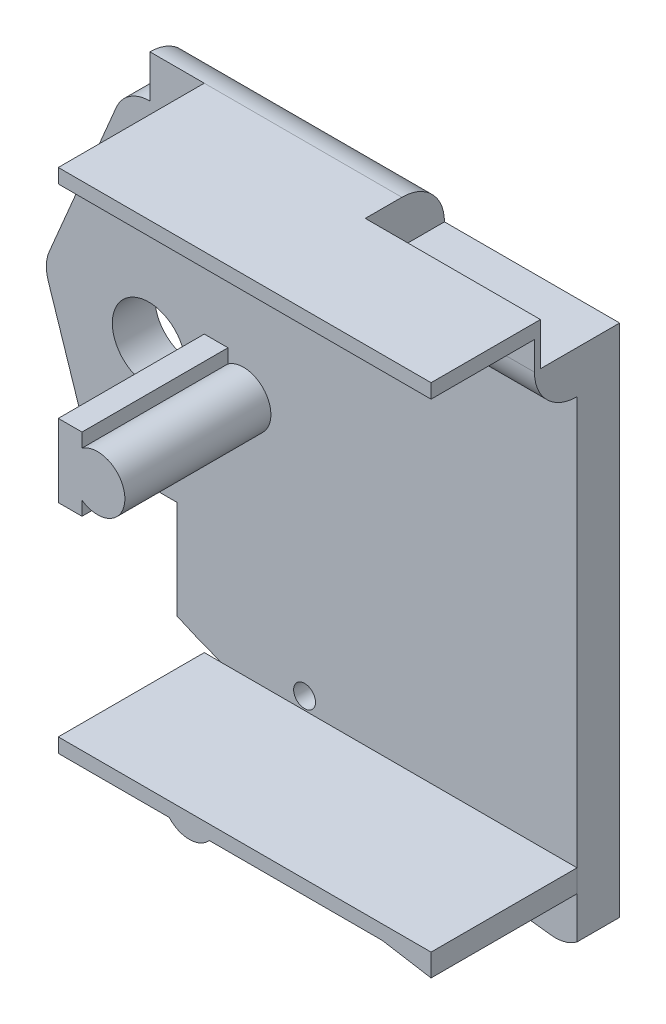
SolidWorks part; units mm, degrees
ref_plane "Спереди" through (0, 0, 0) normal (0, 0, 1) x (1, 0, 0)
ref_plane "Сверху" through (0, 0, 0) normal (0, 1, 0) x (1, 0, 0)
ref_plane "Справа" through (0, 0, 0) normal (1, 0, 0) x (0, 0, -1)
sketch "Эскиз2" plane through (0, 0, 0) normal (0, 0, 1) x (1, 0, 0)
  line L0 (-56.0468, 57.8448) -> (-56.0468, -75.1952)
  line L1 (-186.2888, 51.7421) -> (-204.676, 8.2939)
  line L4 (-193.5028, -33.6946) -> (-169.7062, -33.6946)
  line L5 (-169.7062, -33.6946) -> (-169.7062, -60.6352)
  line L24 (-193.5028, -33.6946) -> (-204.9691, 1.2814)
  line L27 (-177.0796, 57.8448) -> (-56.0468, 57.8448)
  arc A1 (-204.676, 8.2939) -> (-204.9691, 1.2814) centre (-195.4667, 4.3966) ccw
  arc A2 (-186.2888, 51.7421) -> (-177.0796, 57.8448) centre (-177.0796, 47.8448) cw
  arc A3 (-67.1233, -85.137) -> (-56.0468, -75.1952) centre (-66.0468, -75.1952) ccw
  circle A15 centre (-134.7062, -62.1552) radius 3
  spline S1 degree 3 poles (-169.7062, -60.6352) (-159.6635, -65.3294) (-148.3339, -68.8072) (-114.3227, -77.8089) (-90.3681, -82.6201) (-67.1233, -85.137) knots 0.055135 0.055135 0.055135 0.055135 0.172676 0.181905 0.429838 0.429838 0.429838 0.429838
  dimension "D1" = 10
  dimension "D2" = 10
ref_plane "?????25" through (0, 0, 53) normal (0, 0, 1) x (1, 0, 0)
sketch "Эскиз3" plane through (0, 0, 53) normal (0, 0, 1) x (-1, 0, 0)
  line L0 (54.8754, -65.5997) -> (54.8754, -69.5161)
  line L1 (54.8754, 72.6089) -> (54.8754, 65.5997)
  line L3 (155.6874, 10.0166) -> (162.1868, 10.0166)
  line L4 (155.6874, 10.0166) -> (155.6874, 6.196)
  line L6 (155.6874, -9.9834) -> (162.1868, -9.9834)
  line L8 (162.1868, 10.0166) -> (162.1868, -9.9834)
  line L10 (155.6874, -6.1628) -> (155.6874, -9.9834)
  line L15 (204.9076, -65.5997) -> (54.8754, -65.5997)
  line L16 (204.6318, -69.5161) -> (204.9076, -65.5997)
  line L17 (204.6318, -69.5161) -> (54.8754, -69.5161)
  line L19 (133.5844, 65.5997) -> (54.8754, 65.5997)
  line L20 (204.9076, 65.5997) -> (133.5844, 65.5997)
  line L21 (204.6318, 69.5161) -> (204.9076, 65.5997)
  line L22 (131.7963, 69.5161) -> (204.6318, 69.5161)
  line L23 (73.4325, 69.5161) -> (120.8114, 69.5161)
  line L25 (73.4325, 69.5161) -> (54.8754, 72.6089)
  arc A0 (155.6874, 6.196) -> (155.6874, -6.1628) centre (151.4371, 0.0166) ccw
  arc A7 (120.8114, 69.5161) -> (131.7963, 69.5161) centre (126.3039, 64.642) cw
  point P4 (158.9371, 0.0166)
  dimension "D1" = 15
  dimension "D2" = 20
extrude "Бобышка-Вытянуть1" add sketch "Эскиз3" against normal blind 40
extrude "Бобышка-Вытянуть2" add sketch "Эскиз2" along normal blind 13 separate body
sketch "Эскиз4" plane through (-56.0468, 0, 0) normal (1, 0, 0) x (0, 0, -1)
  line L0 (-21.7224, 65.5997) -> (-13, 65.5997)
  line L2 (-13, 65.5997) -> (-13, 57.8448)
  line L3 (-13, 57.8448) -> (-1.3287, 57.8448)
  arc A0 (-1.3287, 57.8448) -> (-21.7224, 65.5997) centre (-13, 57.8448) ccw
extrude "Бобышка-Вытянуть3" add sketch "Эскиз4" against normal up to vertex (148.8609 mm away) up to point (-204.9076, 65.5997, 53)
sketch "Эскиз5" plane through (-56.0468, 0, 0) normal (1, 0, 0) x (0, 0, -1)
  line L0 (-13, 69.5161) -> (-24.6713, 69.5161)
  line L1 (-13, 69.5161) -> (-53, 69.5161) construction
  line L2 (-24.6713, 69.5161) -> (-24.6713, 57.8448)
  arc A0 (-24.6713, 57.8448) -> (-13, 69.5161) centre (-13, 57.8448) ccw
extrude "Бобышка-Вытянуть4" add sketch "Эскиз5" against normal blind 55
sketch "Эскиз6" plane through (-56.0468, 0, 0) normal (1, 0, 0) x (0, 0, -1)
  line L0 (-23.0301, 57.8448) -> (-23.0301, 69.5161)
  line L1 (-13, 69.5161) -> (-53, 69.5161) construction
  line L2 (-23.0301, 69.5161) -> (0, 69.5161)
  line L3 (0, 69.5161) -> (0, 57.8448)
  line L4 (0, 57.8448) -> (-23.0301, 57.8448)
extrude "Вырез-Вытянуть1" cut sketch "Эскиз6" against normal blind 52
sketch "Эскиз7" plane through (0, 0, 13) normal (0, 0, -1) x (-1, 0, 0)
  line L1 (54.8754, 69.5161) -> (56.0468, 69.5161)
  line L2 (54.8754, 69.5161) -> (54.8754, 65.5997)
  line L3 (54.8754, 65.5997) -> (56.0468, 65.5997)
  line L4 (56.0468, 69.5161) -> (56.0468, 65.5997)
extrude "Вырез-Вытянуть2" cut sketch "Эскиз7" against normal blind 52
sketch "Эскиз8" plane through (0, 0, 13) normal (0, 0, -1) x (-1, 0, 0)
  line L0 (56.0468, -75.1952) -> (56.0468, 57.8448) construction
  line L1 (54.8754, -65.5997) -> (56.0468, -65.5997)
  line L2 (54.8754, -65.5997) -> (54.8754, -72.6441)
  line L3 (54.8754, -72.6441) -> (56.0468, -72.6441)
  line L4 (56.0468, -65.5997) -> (56.0468, -72.6441)
extrude "Вырез-Вытянуть3" cut sketch "Эскиз8" against normal blind 52
sketch "Эскиз9" plane through (0, 0, 53) normal (0, 0, 1) x (1, 0, 0)
  line L0 (-162.1868, 9.8124) -> (-162.1868, 78.3892)
  line L1 (-162.1868, 9.9834) -> (-162.1868, -10.0166) construction
  line L2 (-162.1868, 78.3892) -> (-213.7657, 78.3892)
  line L3 (-213.7657, 78.3892) -> (-213.7657, -81.2546)
  line L4 (-213.7657, -81.2546) -> (-162.1868, -81.2546)
  line L5 (-162.1868, -81.2546) -> (-162.1868, 9.8124)
extrude "Вырез-Вытянуть4" cut sketch "Эскиз9" against normal blind 40
sketch "Эскиз11" plane through (-56.0468, 0, 0) normal (1, 0, 0) x (0, 0, -1)
  line L0 (-1.3287, 57.8448) -> (0, 57.8448)
  line L1 (0, 57.8448) -> (0, -90.6618)
  line L2 (0, -90.6618) -> (-1.3287, -90.6618)
  line L3 (-1.3287, -90.6618) -> (-1.3287, 57.8448)
extrude "Вырез-Вытянуть5" cut sketch "Эскиз11" against normal blind 160
sketch "Эскиз12" plane through (0, 0, 1.3287) normal (0, 0, -1) x (-1, 0, 0)
  line L1 (56.0468, 69.5161) -> (60.0468, 69.5161)
  line L2 (56.0468, 69.5161) -> (56.0468, -92.7652)
  line L3 (56.0468, -92.7652) -> (60.0468, -92.7652)
  line L4 (60.0468, 69.5161) -> (60.0468, -92.7652)
  dimension "D1" = 4
extrude "Вырез-Вытянуть6" cut sketch "Эскиз12" against normal blind 160
sketch "Эскиз13" plane through (0, 0, 1.3287) normal (0, 0, -1) x (-1, 0, 0)
  circle A0 centre (177.3858, -0.0057) radius 10
extrude "Вырез-Вытянуть8" cut sketch "Эскиз13" against normal blind 32
sketch "Эскиз14" plane through (0, 0, 13) normal (0, 0, 1) x (1, 0, 0)
  line L0 (-177.0796, 57.8448) -> (-177.0796, 69.5161)
  line L1 (-204.9076, 69.5161) -> (-162.1868, 69.5161) construction
  line L2 (-177.0796, 69.5161) -> (-204.9076, 69.5161)
  line L3 (-204.9076, 69.5161) -> (-204.9076, 57.8448)
  line L4 (-204.9076, 57.8448) -> (-177.0796, 57.8448)
extrude "Вырез-Вытянуть9" cut sketch "Эскиз14" against normal blind 18
